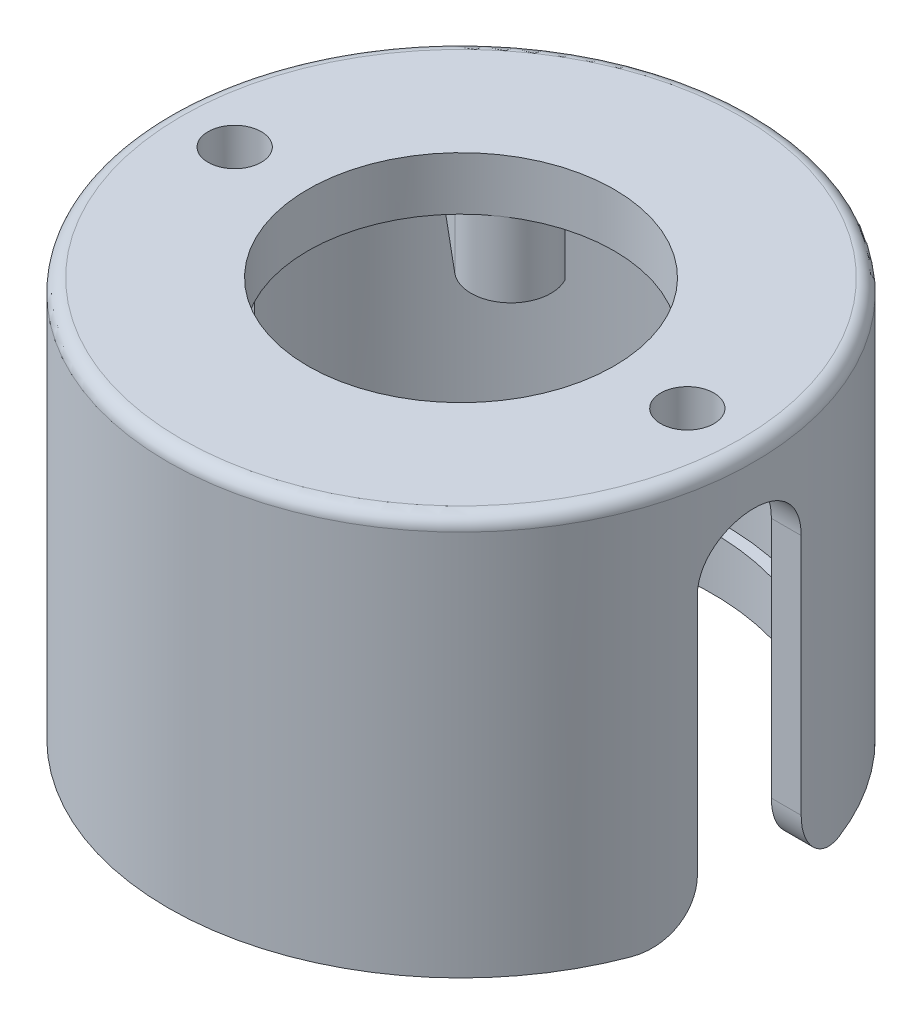
SolidWorks part; units mm, degrees
ref_plane "Alzado" through (0, 0, 0) normal (0, 0, 1) x (1, 0, 0)
ref_plane "Planta" through (0, 0, 0) normal (0, 1, 0) x (1, 0, 0)
ref_plane "Vista lateral" through (0, 0, 0) normal (1, 0, 0) x (0, 0, -1)
sketch "Croquis1" plane through (0, 0, 0) normal (0, 1, 0) x (1, 0, 0)
  line L0 (-10.8258, 1.95) -> (10.8258, 1.95) construction
  line L1 (10.8258, -1.95) -> (-10.8258, -1.95) construction
  line L2 (10.8258, 1.95) -> (9.7061, 1.95)
  line L3 (9.7061, -1.95) -> (10.8258, -1.95)
  line L4 (10.8258, -1.95) -> (10.9357, -1.8905)
  line L5 (-9.7061, 1.95) -> (-10.8258, 1.95)
  line L6 (-10.8258, -1.95) -> (-9.7061, -1.95)
  arc A0 (-10.8258, -1.95) -> (10.8258, -1.95) centre (0, 0) ccw
  arc A1 (-9.7061, -1.95) -> (9.7061, -1.95) centre (0, 0) ccw
  arc A2 (9.7061, 1.95) -> (-9.7061, 1.95) centre (0, 0) ccw
  arc A3 (10.8258, 1.95) -> (-10.8258, 1.95) centre (0, 0) ccw
  dimension "D1" = 22
  dimension "D3" = 19.8
  dimension "D2" = 3.9
extrude "Saliente-Extruir1" add sketch "Croquis1" against normal blind 13 contours A1 L6 A0 L3 | L2 A3 L5 A2 region at (10.2659, 0, -2.1847) region at (10.2659, 0, 2.1847)
sketch "Croquis2" plane through (0, 0, 0) normal (0, 1, 0) x (1, 0, 0)
  circle A0 centre (0, 0) radius 11
  circle A1 centre (0, 0) radius 5.75
  dimension "D1" = 11.5
extrude "Saliente-Extruir3" add sketch "Croquis2" along normal blind 2
fillet "Redondeo4" radius 1.95 8 edges at (-10.2659, 0, -1.95) (-10.2659, -13, 1.95) (-10.2659, -13, -1.95) (10.2659, -13, 1.95) (10.2659, -13, -1.95) (10.2659, 0, -1.95)
fillet "Redondeo5" radius 0.5 1 edges at (0, 2, 11)
sketch "Croquis5" plane through (0, 0, 0) normal (0, -1, 0) x (1, 0, 0)
  line L0 (-9.9, 0) -> (9.9, 0) construction
  line L1 (0, 9.9) -> (0, -9.9) construction
  line L2 (2.7724, -6.6774) -> (5, -8.5446)
  line L3 (5.0636, -4.8297) -> (7.2912, -6.6969)
  line L4 (5.0636, 4.8297) -> (7.2912, 6.6969)
  line L5 (2.7724, 6.6774) -> (5, 8.5446)
  line L6 (-2.7724, 6.6774) -> (-5, 8.5446)
  line L7 (-5.0636, 4.8297) -> (-7.2912, 6.6969)
  line L8 (-5.0636, -4.8297) -> (-7.2912, -6.6969)
  line L9 (-2.7724, -6.6774) -> (-5, -8.5446)
  circle A0 centre (4.1, -5.9793) radius 1.5
  arc A1 (9.0995, 3.9) -> (-9.0995, 3.9) centre (0, 0) ccw construction
  arc A2 (-9.9, 0) -> (9.9, 0) centre (0, 0) ccw construction
  circle A3 centre (0, 0) radius 5.75 construction
  circle A4 centre (4.1, 5.9793) radius 1.5
  circle A5 centre (-4.1, 5.9793) radius 1.5
  circle A6 centre (-4.1, -5.9793) radius 1.5
  arc M4 (9.9, 0) -> (-9.9, 0) centre (0, 0) ccw
  arc M5 (-9.9, 0) -> (9.9, 0) centre (0, 0) ccw
  dimension "D1" = 3
  dimension "D2" = 8.2
  dimension "D3" = 10
extrude "Saliente-Extruir4" add sketch "Croquis5" along normal blind 2.8 contours A5 L6 L7 M4 | L5 A4 L4 M4 | A4 L5 | A0 L2 L3 M5 | A0 L2 | A6 L9 | L9 A6 L8 M5 | A5 L6 region at (4.1113, 0, -5.9659) region at (5.6956, 0, -7.0833) region at (-5.6956, 0, -7.0833) region at (-4.1113, 0, -5.9659) region at (5.6956, 0, 7.0833) region at (4.1113, 0, 5.9659) region at (-5.6956, 0, 7.0833) region at (-4.1113, 0, 5.9659)
sketch "Croquis6" plane through (0, 2, 0) normal (0, 1, 0) x (1, 0, 0)
  line L0 (-11, 0) -> (10.5, 0) construction
  line L1 (0, -10.5) -> (0, 10.5) construction
  circle A0 centre (0, 0) radius 11 construction
  circle A1 centre (0, 0) radius 10.5 construction
  circle A2 centre (8.5, 0) radius 1
  circle A3 centre (-8.5, 0) radius 1
  dimension "D1" = 17
  dimension "D2" = 2
extrude "Cortar-Extruir1" cut sketch "Croquis6" against normal blind 2.8
sketch "Croquis7" plane through (0, -13, 0) normal (0, -1, 0) x (1, 0, 0)
  line L0 (9.0995, -3.9) -> (10.2854, -3.9)
  line L1 (10.2854, 3.9) -> (9.0995, 3.9)
  line L2 (-9.0995, 3.9) -> (-10.2854, 3.9)
  line L3 (-9.0995, -3.9) -> (-10.2854, -3.9)
  line L4 (9.0995, -3.9) -> (8.5995, -3.9)
  line L5 (-8.5995, 3.9) -> (-9.0995, 3.9)
  line L6 (-8.5995, -3.9) -> (-9.0995, -3.9)
  line L7 (8.5995, 3.9) -> (9.0995, 3.9)
  arc A0 (-10.2854, -3.9) -> (10.2854, -3.9) centre (0, 0) ccw
  arc A1 (9.9, 0) -> (7.2912, 6.6969) centre (0, 0) ccw construction
  arc A2 (9.7061, 1.95) -> (9.0995, 3.9) centre (0, 0) ccw construction
  arc A3 (10.2854, 3.9) -> (-10.2854, 3.9) centre (0, 0) ccw
  arc A4 (8.5995, 3.9) -> (-8.5995, 3.9) centre (0, 0) ccw
  arc A5 (-8.5995, -3.9) -> (8.5995, -3.9) centre (0, 0) ccw
  dimension "D1" = 0.5
extrude "Saliente-Extruir5" add sketch "Croquis7" against normal blind 2
